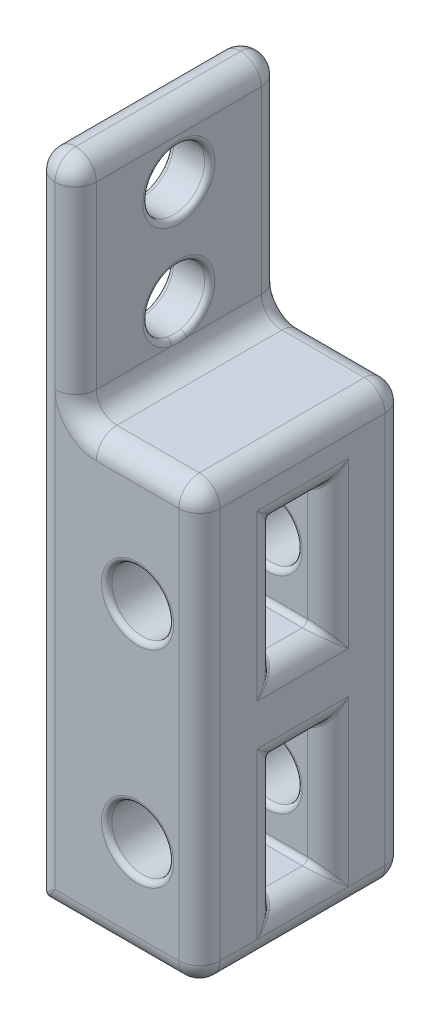
SolidWorks part; units mm, degrees
ref_plane "Plan de face" through (0, 0, 0) normal (0, 0, 1) x (1, 0, 0)
ref_plane "Plan de dessus" through (0, 0, 0) normal (0, 1, 0) x (1, 0, 0)
ref_plane "Plan de droite" through (0, 0, 0) normal (1, 0, 0) x (0, 0, -1)
sketch "Esquisse1" plane through (0, 0, 0) normal (0, 0, 1) x (1, 0, 0)
  line L1 (4, -10.5) -> (-4, -10.5)
  line L2 (4, -10.5) -> (4, 10.5)
  line L3 (4, 10.5) -> (-4, 10.5)
  line L4 (-4, -10.5) -> (-4, 10.5)
  line L5 (4, -10.5) -> (-4, 10.5) construction
  line L6 (4, 10.5) -> (-4, -10.5) construction
  line L7 (-4, 10.5) -> (-2, 10.5)
  line L9 (-4, 10.5) -> (-4, 21.2086)
  line L10 (-4, 21.2086) -> (-2, 21.2086)
  line L12 (-2, 10.5) -> (-2, 21.2086)
  point P0 (0, 0)
  dimension "D1" = 21
  dimension "D2" = 8
  dimension "D3" = 2
extrude "Boss.-Extru.1" add sketch "Esquisse1" along normal blind 10 contours L10 L2 L3 L4 L1 | L9 L7 L12 L10 region at (0, 0, 0)
sketch "Esquisse2" plane through (0, 10.5, 0) normal (0, 1, 0) x (1, 0, 0)
  line L0 (-4, -5) -> (4, -5)
  line L1 (-4, -10) -> (-4, 0) construction
  line L2 (4, -10) -> (4, 0) construction
sketch3d "Esquisse3D1"
  line L0 (-4, 10.5, 5) -> (4, 10.5, 5) construction
sketch "Esquisse3" plane through (0, 0, 5) normal (0, 0, 1) x (1, 0, 0)
  line L0 (1, 10.5) -> (1, -10.5) construction
  line L13 (2.7321, 7.5) -> (5.2514, 7.5)
  line L15 (2.7321, 7.5) -> (-0.7321, 7.5)
  line L16 (-4, 10.5) -> (4, 10.5) construction
  line L17 (4, -10.5) -> (-4, -10.5) construction
  line L18 (-4, -10.5) -> (-4, 21.2086) construction
  line L19 (-0.7321, 7.5) -> (-2.4641, 4.5)
  line L20 (-2.4641, 4.5) -> (-0.7321, 1.5)
  line L21 (-0.7321, 1.5) -> (2.7321, 1.5)
  line L24 (2.7321, -2.5) -> (-0.7321, -2.5)
  line L25 (-0.7321, -2.5) -> (-2.4641, -5.5)
  line L26 (-2.4641, -5.5) -> (-0.7321, -8.5)
  line L27 (-0.7321, -8.5) -> (2.7321, -8.5)
  line L29 (5.2514, 7.5) -> (5.2514, 1.5)
  line L30 (5.2514, 1.5) -> (2.7321, 1.5)
  line L31 (2.7321, -2.5) -> (5.2514, -2.5)
  line L32 (5.2514, -2.5) -> (5.2514, -8.5)
  line L33 (5.2514, -8.5) -> (2.7321, -8.5)
  line L35 (4.4641, 4.5) -> (3.5981, 6) [skipped]
  line L36 (2.7321, 1.5) -> (3.5981, 3) [skipped]
  line L37 (4.4641, -5.5) -> (3.5981, -4) [skipped]
  line L38 (2.7321, -8.5) -> (3.5981, -7) [skipped]
  circle A1 centre (1, -5.5) radius 1.5
  circle A2 centre (1, 4.5) radius 1.5
  circle A3 centre (1, 4.5) radius 3 construction
  circle A4 centre (1, -5.5) radius 3 construction
  dimension "D1" = 3
  dimension "D2" = 3
  dimension "D3" = 6
  dimension "D4" = 5
  dimension "D5" = 6
  dimension "D6" = 5
  dimension "D7" = 10
extrude "Enlèv. mat.-Extru.1" cut sketch "Esquisse3" against normal blind 1.24 and the other way blind 1.2 contours A2 | A1 | L21 L20 L19 L15 L13 L29 L30 | L33 L32 L31 L24 L25 L26 L27
sketch "Esquisse5" plane through (0, 0, 10) normal (0, 0, 1) x (1, 0, 0)
  line L0 (1, -10.5) -> (1, 10.5) construction
  line L1 (4, -10.5) -> (-4, -10.5) construction
  line L2 (-4, 10.5) -> (4, 10.5) construction
  line L3 (-4, -10.5) -> (-4, 21.2086) construction
  circle A0 centre (1, 4.5) radius 1.5
  circle A1 centre (1, -5.5) radius 1.5
  dimension "D4" = 10
  dimension "D1" = 3
  dimension "D5" = 3
  dimension "D2" = 5
  dimension "D3" = 5
extrude "Enlèv. mat.-Extru.2" cut sketch "Esquisse5" against normal up to next
sketch "Esquisse6" plane through (-2, 0, 0) normal (1, 0, 0) x (0, 0, -1)
  line L0 (-5, 21.2086) -> (-5, 10.4104) construction
  line L1 (-10, 21.2086) -> (0, 21.2086) construction
  circle A0 centre (-5, 18.2086) radius 1.5
  circle A1 centre (-5, 13.2086) radius 1.5
  dimension "D1" = 3
  dimension "D2" = 3
  dimension "D3" = 3
  dimension "D4" = 5
extrude "Enlèv. mat.-Extru.3" cut sketch "Esquisse6" against normal up to next contours A1 | A0
fillet "Congé2" radius 1 23 edges at (-2, 15.8543, 0) (-2, 15.8543, 10) (-2, 21.2086, 5) (-4, 21.2086, 5) (4, -8.5, 4.98) (4, -5.5, 3.76) (4, -2.5, 4.98) (4, -5.5, 6.2) (4, -10.5, 5) (4, 0, 10) (4, 0, 0) (4, 4.5, 3.76) (4, 7.5, 4.98) (4, 4.5, 6.2) (4, 1.5, 4.98) (1, 10.5, 0) (4, 10.5, 5) (1, 10.5, 10) (-2, 10.5, 5) (-4, 5.3543, 0) (0, -10.5, 0) (0, -10.5, 10) (-4, 5.3543, 10)
fillet "Congé3" radius 0.25 45 edges at (3.7071, 7.7929, 3.4671) (3.7071, 1.2071, 3.4671) (3.7071, -2.2071, 3.4671) (3.7071, -8.7929, 3.4671) (3.7071, -8.7929, 6.4929) (3.7071, -2.2071, 6.4929) (3.7071, 1.2071, 6.4929) (3.7071, 7.7929, 6.4929) (-3.7071, -10.2071, 9.7071) (-3.7071, -10.2071, 0.2929) (-0.7321, -2.5, 4.98) (-2.4641, -5.5, 4.98) (-0.7321, -8.5, 4.98) (-0.7321, 7.5, 4.98) (-0.7321, 1.5, 4.98) (-2.4641, 4.5, 4.98) (-1.5981, 3, 3.76) (-1.5981, 6, 3.76) (1.134, 7.5, 3.76) (1.134, 1.5, 3.76) (2.5, 4.5, 3.76) (-1.5981, -7, 3.76) (-1.5981, -4, 3.76) (1.134, -2.5, 3.76) (1.134, -8.5, 3.76) (-0.5, -5.5, 3.76) (2.5, -5.5, 0) (2.5, 4.5, 0) (-1.5981, -4, 6.2) (-1.5981, -7, 6.2) (1.134, -8.5, 6.2) (1.134, -2.5, 6.2) (-0.5, -5.5, 6.2) (-1.5981, 6, 6.2) (-1.5981, 3, 6.2) (1.134, 1.5, 6.2) (1.134, 7.5, 6.2) (2.5, 4.5, 6.2) (2.5, -5.5, 10) (2.5, 4.5, 10) (-4, -10.5, 5) (-4, 18.2086, 6.5) (-4, 13.2086, 6.5) (-2, 18.2086, 3.5) (-2, 13.2086, 3.5)
